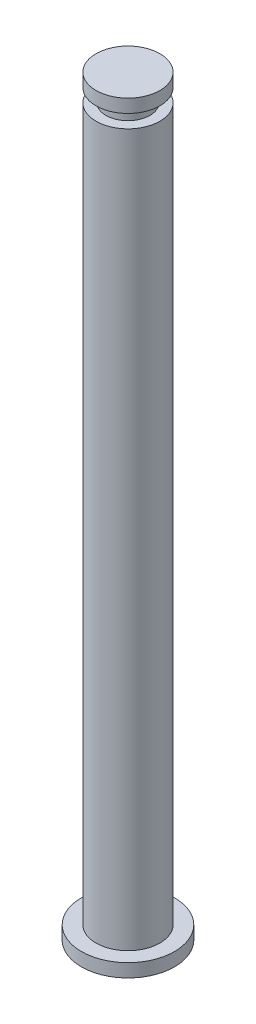
SolidWorks part; units mm, degrees
ref_plane "Alzado" through (0, 0, 0) normal (0, 0, 1) x (1, 0, 0)
ref_plane "Planta" through (0, 0, 0) normal (0, 1, 0) x (1, 0, 0)
ref_plane "Vista lateral" through (0, 0, 0) normal (1, 0, 0) x (0, 0, -1)
sketch "Croquis1" plane through (0, 0, 0) normal (0, 1, 0) x (1, 0, 0)
  circle A0 centre (0, 0) radius 3.5
  circle A1 centre (0, 0) radius 2.4
  dimension "D1" = 7
  dimension "D2" = 4.8
extrude "Saliente-Extruir1" add sketch "Croquis1" along normal blind 1
extrude "Saliente-Extruir2" add sketch "Croquis1<2>" along normal blind 56.5 contours A1 region at (0, 0, 0)
sketch "Croquis1<2>" plane through (0, 0, 0) normal (0, 1, 0) x (1, 0, 0) same geometry as "Croquis1"
sketch "Croquis2" plane through (0, 56.5, 0) normal (0, 1, 0) x (1, 0, 0)
  circle A0 centre (0, 0) radius 1.65
  circle A2 centre (0, 0) radius 2.4
  circle A3 centre (0, 0) radius 2.4
  dimension "D2" = 0.75
  dimension "D1" = 0
extrude "Cortar-Extruir1" cut sketch "Croquis2" against normal blind 1 from offset 1 offset against normal yes
